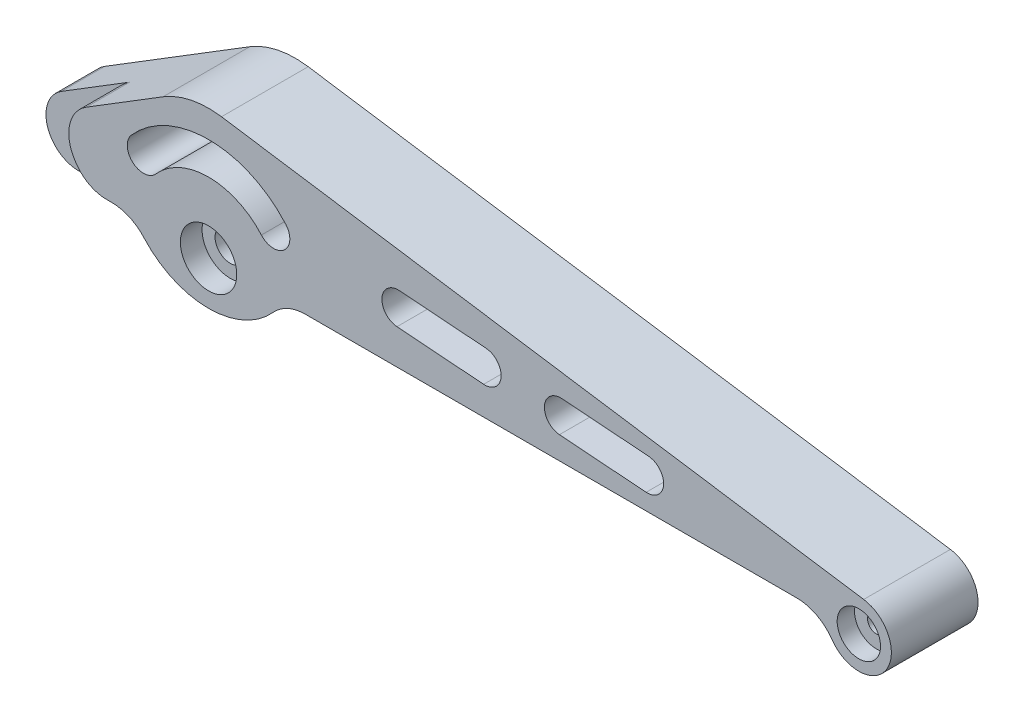
SolidWorks part; units mm, degrees
ref_plane "Front Plane" through (0, 0, 0) normal (0, 0, 1) x (1, 0, 0)
ref_plane "Top Plane" through (0, 0, 0) normal (0, 1, 0) x (1, 0, 0)
ref_plane "Right Plane" through (0, 0, 0) normal (1, 0, 0) x (0, 0, -1)
sketch "Sketch1" plane through (0, 0, 0) normal (0, 0, 1) x (1, 0, 0)
  line L0 (0, 0) -> (150, 0) construction
  line L1 (0, 0) -> (-40, 0) construction
  line L2 (-32.5, 0) -> (-10, 0)
  line L3 (10, 0) -> (142.5, 0)
  line L4 (-43.9393, 6.3822) -> (-10.5048, 27.0191)
  line L5 (2.9851, 29.776) -> (151.1194, 7.416)
  line L6 (0, 10) -> (0, 30) construction
  line L7 (20, 10) -> (20, 0) construction
  line L8 (80, 0) -> (80, 18.151) construction
  line L9 (20, 0) -> (20, 27.2077) construction
  line L10 (20, 13.6038) -> (80, 9.0755) construction
  line L11 (80, 9.0755) -> (142.5, 4.3585) construction
  line L12 (142.5, 4.3585) -> (142.5, 0) construction
  line L13 (43.7394, 11.8122) -> (63.7394, 10.3027) construction
  line L14 (44.0216, 15.5515) -> (64.0216, 14.0421)
  line L15 (43.4571, 8.0728) -> (63.4571, 6.5634)
  line L16 (81.2181, 8.9836) -> (101.2181, 7.4741) construction
  line L17 (81.5003, 12.723) -> (101.5003, 11.2135)
  line L18 (80.9359, 5.2442) -> (100.9359, 3.7348)
  circle A0 centre (0, 0) radius 3.5
  circle A1 centre (150, 0) radius 2
  circle A2 centre (-40, 0) radius 2
  circle A3 centre (0, 0) radius 6
  circle A4 centre (0, 0) radius 10
  circle A5 centre (-40, 0) radius 5
  circle A6 centre (150, 0) radius 5
  circle A7 centre (-40, 0) radius 7.5
  circle A8 centre (150, 0) radius 7.5
  circle A9 centre (0, 10) radius 20
  arc A10 (-20, 0) -> (20, 0) centre (0, 0) cw
  arc A11 (-15, 13.2288) -> (15, 13.2288) centre (0, 0) cw construction
  arc A12 (17.8125, 15.7091) -> (-17.8125, 15.7091) centre (0, 0) ccw
  arc A13 (12.1875, 10.7484) -> (-12.1875, 10.7484) centre (0, 0) ccw
  arc A14 (12.1875, 10.7484) -> (17.8125, 15.7091) centre (15, 13.2288) ccw
  arc A15 (-17.8125, 15.7091) -> (-12.1875, 10.7484) centre (-15, 13.2288) ccw
  arc A16 (44.0216, 15.5515) -> (43.4571, 8.0728) centre (43.7394, 11.8122) ccw
  arc A17 (63.4571, 6.5634) -> (64.0216, 14.0421) centre (63.7394, 10.3027) ccw
  arc A18 (81.5003, 12.723) -> (80.9359, 5.2442) centre (81.2181, 8.9836) ccw
  arc A19 (100.9359, 3.7348) -> (101.5003, 11.2135) centre (101.2181, 7.4741) ccw
  point P27 (0, 20)
  point P28 (0, 20)
  point P32 (0, 20)
  point P47 (53.7394, 11.0575)
  point P54 (91.2181, 8.2289)
  point P59 (40, 12.0944)
  point P60 (67.4787, 10.0205)
  point P61 (77.4787, 9.2658)
  dimension "D3" = 7
  dimension "D4" = 4
  dimension "D5" = 4
  dimension "D6" = 12
  dimension "D7" = 20
  dimension "D8" = 10
  dimension "D9" = 10
  dimension "D10" = 15
  dimension "D11" = 15
  dimension "D12" = 20
  dimension "D14" = 7.5
  dimension "D1" = 150
  dimension "D2" = 40
  dimension "D13" = 20
  dimension "D15" = 15
  dimension "D16" = 0
  dimension "D17" = 60
  dimension "D18" = 7.5
  dimension "D19" = 7.5
  dimension "D20" = 20
  dimension "D21" = 10
  dimension "D22" = 20
  dimension "D23" = 20
extrude "Boss-Extrude1" add sketch "Sketch1" along normal blind 20 contours A9 A10 L3 A8 L5 A19 L18 A18 L17 A17 L15 A16 L14 | A8 A6 | A6 A1 | A10 A9 L3 | A4 A9 L3 | A15 A10 A9 L2 A4 L3 A14 A13 | A15 A12 A14 A10 A9 | L2 A9 A4 | A4 A3 | A0 | A3 A0 | A10 L2 A9 | L2 A10 A9 L4 A7 | A7 A5 | A5 A2
fillet "Fillet1" radius 10 4 edges at (-32.5, 0, 10) (-17.3205, 0, 10) (17.3205, 0, 10) (142.5, 0, 10)
sketch "Sketch2" plane through (0, 0, 20) normal (0, 0, 1) x (1, 0, 0)
  line L0 (-35.3865, 11.6613) -> (-28.1086, -0.3098)
  line L1 (-43.9393, 6.3822) -> (-10.5048, 27.0191) construction
  circle A0 centre (-40, 0) radius 10
  arc A1 (-25.6386, 0) -> (-33.8451, -4.2857) centre (-25.6386, -10) ccw construction
  circle M2 centre (-40, 0) radius 2
  arc M16 (-43.9393, 6.3822) -> (-33.8451, -4.2857) centre (-40, 0) ccw
  arc M17 (-33.8451, -4.2857) -> (-25.6386, 0) centre (-25.6386, -10) cw
  line M27 (-10.5048, 27.0191) -> (-43.9393, 6.3822)
  dimension "D1" = 20
extrude "Cut-Extrude4" cut sketch "Sketch2" against normal blind 10 contours A0 M27 M16 M17 M2 | A0 L0 M27 | A0 L0 M17
fillet "Fillet3" radius 8.5 2 edges at (-35.3865, 11.6613, 15) (-28.1086, -0.3098, 15)
sketch "Sketch3" plane through (0, 0, 20) normal (0, 0, 1) x (1, 0, 0)
  circle A0 centre (0, 0) radius 6.5
  circle A1 centre (150, 0) radius 5
  dimension "D1" = 13
  dimension "D2" = 10
extrude "Cut-Extrude5" cut sketch "Sketch3" against normal blind 5 contours A0
sketch "Sketch5" plane through (0, 0, 0) normal (0, 0, -1) x (-1, 0, 0)
  circle A0 centre (0, 0) radius 6.5
  circle A1 centre (-150, 0) radius 5
  circle A2 centre (40, 0) radius 5
  dimension "D1" = 10
  dimension "D2" = 13
  dimension "D3" = 10
extrude "Cut-Extrude7" cut sketch "Sketch5" against normal blind 5 contours A0
sketch "Sketch7" plane through (0, 0, 0) normal (0, 0, -1) x (-1, 0, 0)
  circle A0 centre (-150, 0) radius 5
  circle A1 centre (40, 0) radius 5
  dimension "D1" = 10
  dimension "D2" = 10
extrude "Cut-Extrude8" cut sketch "Sketch7" against normal blind 4
sketch "Sketch8" plane through (0, 0, 20) normal (0, 0, 1) x (1, 0, 0)
  circle A0 centre (150, 0) radius 5
  dimension "D1" = 10
extrude "Cut-Extrude9" cut sketch "Sketch8" against normal blind 4
